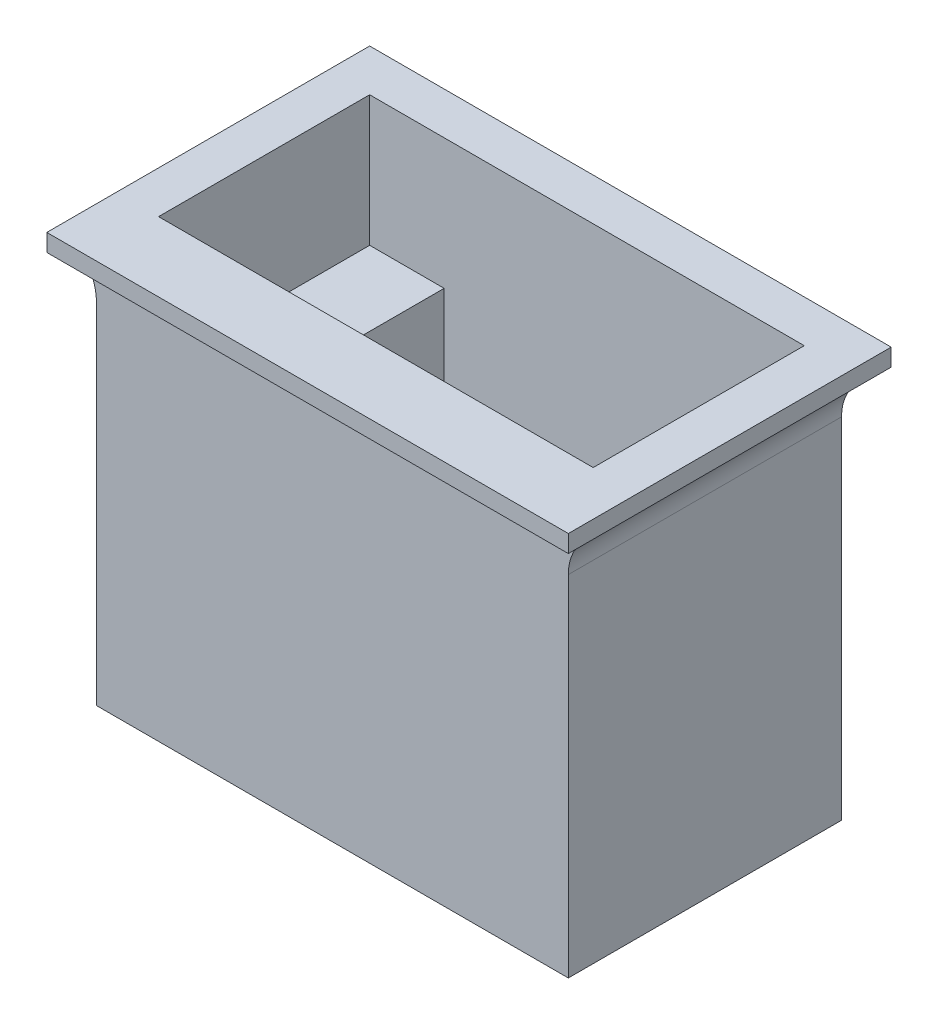
SolidWorks part; units mm, degrees
ref_plane "Front Plane" through (0, 0, 0) normal (0, 0, 1) x (1, 0, 0)
ref_plane "Top Plane" through (0, 0, 0) normal (0, 1, 0) x (1, 0, 0)
ref_plane "Right Plane" through (0, 0, 0) normal (1, 0, 0) x (0, 0, -1)
sketch "Sketch1" plane through (0, 0, 0) normal (0, 1, 0) x (1, 0, 0)
  line L0 (8.6, 5.9429) -> (8.6, -20.9814) construction
  line L1 (-10.4, 5.9429) -> (27.6, 5.9429)
  line L2 (-10.4, 5.9429) -> (-10.4, -16.0571)
  line L3 (-10.4, -16.0571) -> (27.6, -16.0571)
  line L4 (27.6, 5.9429) -> (27.6, -16.0571)
  dimension "D1" = 38
  dimension "D2" = 22
extrude "Boss-Extrude1" add sketch "Sketch1" along normal blind 33
sketch "Sketch2" plane through (0, 33, 0) normal (0, 1, 0) x (1, 0, 0)
  line L0 (27.6, 5.9429) -> (-10.4, 5.9429) construction
  line L1 (-9, 4.5429) -> (26, 4.5429)
  line L2 (-9, 4.5429) -> (-9, -12.4571)
  line L3 (-9, -12.4571) -> (26, -12.4571)
  line L4 (26, 4.5429) -> (26, -12.4571)
  line L5 (-10.4, 5.9429) -> (-10.4, -16.0571) construction
  dimension "D1" = 35
  dimension "D2" = 17
  dimension "D3" = 1.4
  dimension "D4" = 1.4
extrude "Cut-Extrude1" cut sketch "Sketch2" against normal blind 28
sketch "Sketch3" plane through (0, 5, 0) normal (0, 1, 0) x (1, 0, 0)
  line L0 (-9, -12.4571) -> (26, -12.4571) construction
  line L1 (-9, 4.5429) -> (-3, 4.5429)
  line L2 (-9, 4.5429) -> (-9, -12.4571)
  line L3 (-9, -12.4571) -> (-3, -12.4571)
  line L4 (-3, 4.5429) -> (-3, -12.4571)
  line L5 (26, 4.5429) -> (-9, 4.5429) construction
  line L6 (20, 4.5429) -> (26, 4.5429)
  line L7 (20, 4.5429) -> (20, -12.4571)
  line L8 (20, -12.4571) -> (26, -12.4571)
  line L9 (26, 4.5429) -> (26, -12.4571)
  dimension "D1" = 6
  dimension "D2" = 6
extrude "Boss-Extrude2" add sketch "Sketch3" along normal blind 17.5
sketch "Sketch4" plane through (0, 33, 0) normal (0, 1, 0) x (1, 0, 0)
  line L1 (-10.4, 5.9429) -> (27.6, 5.9429)
  line L2 (-10.4, 5.9429) -> (-10.4, -16.0571)
  line L3 (-10.4, -16.0571) -> (27.6, -16.0571)
  line L4 (27.6, 5.9429) -> (27.6, -16.0571)
extrude "Extrude-Thin2" add sketch "Sketch4" against normal blind 1.4 thin thin type one direction wall 2
sketch "Sketch5" plane through (0, 22.5, 0) normal (0, 1, 0) x (1, 0, 0)
  line L0 (-3, -12.4571) -> (-3, 4.5429) construction
  circle A0 centre (-5.5, -3.8921) radius 1
  dimension "D1" = 2
  dimension "D2" = 2.5
extrude "Cut-Extrude2" cut sketch "Sketch5" against normal blind 3
sketch "Sketch6" plane through (0, 22.5, 0) normal (0, 1, 0) x (1, 0, 0)
  circle A0 centre (22.9531, -4.1157) radius 1
  dimension "D1" = 2
extrude "Cut-Extrude3" cut sketch "Sketch6" against normal blind 3
sketch "Sketch7" plane through (-3, 0, 0) normal (1, 0, 0) x (0, 0, -1)
  line L0 (5.9429, 31.6) -> (5.9429, 0) construction
  line L1 (0.9429, 4.0414) -> (-8.4571, 4.0414)
  line L2 (0.9429, 4.0414) -> (0.9429, 8.5414)
  line L3 (0.9429, 8.5414) -> (-8.4571, 8.5414)
  line L4 (-8.4571, 4.0414) -> (-8.4571, 8.5414)
  point P4 (0.9429, 6.2914)
  dimension "D1" = 9.4
  dimension "D2" = 4.5
  dimension "D3" = 5
extrude "Cut-Extrude4" cut sketch "Sketch7" against normal blind 10
sketch "Sketch8" plane through (0, 5, 0) normal (0, 1, 0) x (1, 0, 0)
  line L1 (-1.4079, -8.7279) -> (18.5921, -8.7279)
  line L2 (-1.4079, -8.7279) -> (-1.4079, 1.2721)
  line L3 (-1.4079, 1.2721) -> (18.5921, 1.2721)
  line L4 (18.5921, -8.7279) -> (18.5921, 1.2721)
  dimension "D1" = 10
  dimension "D2" = 20
extrude "Cut-Extrude5" cut sketch "Sketch8" against normal blind 3.5
sketch "Sketch9" plane through (0, 1.5, 0) normal (0, 1, 0) x (1, 0, 0)
  circle A0 centre (8.8083, -3.6349) radius 3.7
  circle A3 centre (1.6083, -3.6349) radius 1
  circle A4 centre (16.0083, -3.6349) radius 1
  dimension "D1" = 7.4
  dimension "D2" = 3.5
  dimension "D5" = 2
  dimension "D4" = 2
  dimension "D3" = 3.5
extrude "Cut-Extrude6" cut sketch "Sketch9" against normal through all
fillet "Fillet1" radius 4 4 edges at (18.5921, 3.25, -1.2721) (18.5921, 3.25, 8.7279) (-1.4079, 3.25, -1.2721) (-1.4079, 3.25, 8.7279)
fillet "Fillet2" radius 3 1 edges at (-3, 8.5414, 3.7571)
fillet "Fillet3" radius 4 2 edges at (-10.4, 31.6, 5.0571) (27.6, 31.6, 5.0571)
